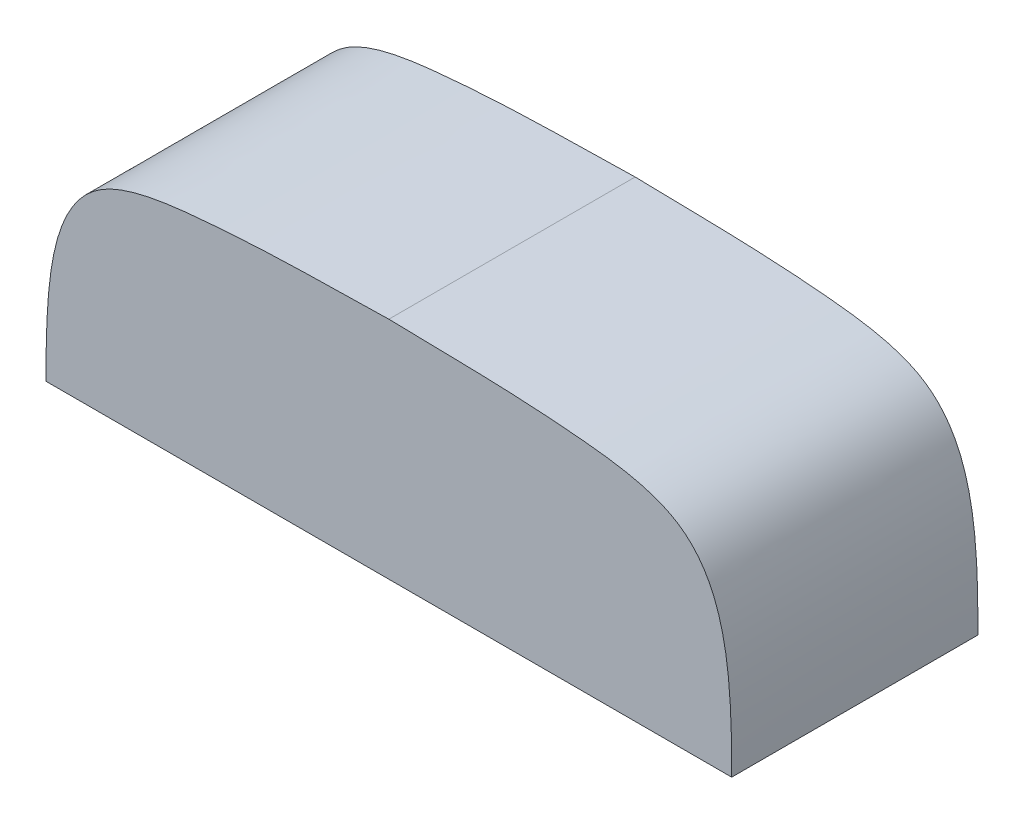
SolidWorks part; units mm, degrees
ref_plane "Front Plane" through (0, 0, 0) normal (0, 0, 1) x (1, 0, 0)
ref_plane "Top Plane" through (0, 0, 0) normal (0, 1, 0) x (1, 0, 0)
ref_plane "Right Plane" through (0, 0, 0) normal (1, 0, 0) x (0, 0, -1)
sketch "Sketch1" plane through (0, 0, 0) normal (0, 0, 1) x (1, 0, 0)
  line L1 (-353.568, 0) -> (353.568, 0)
  spline S0 degree 3 poles (0, 232.2583) (64.4497, 230.6344) (158.6698, 231.088) (348.7113, 205.1798) (353.551, 85.4029) (353.568, 0) knots 0 0 0 0 0.225226 0.33784 0.571999 0.571999 0.571999 0.571999
  spline S1 degree 3 poles (0, 232.2583) (-64.4497, 230.6344) (-158.6698, 231.088) (-348.7113, 205.1798) (-353.551, 85.4029) (-353.568, 0) knots 0 0 0 0 0.225226 0.33784 0.571999 0.571999 0.571999 0.571999
  point P4 (-186.2749, 0.9583)
  point P5 (0, 0)
  point P6 (0, 0)
  point P7 (0, 0)
  point P9 (0, 0)
  point P11 (0, 0)
extrude "Boss-Extrude1" add sketch "Sketch1" along normal blind 254
